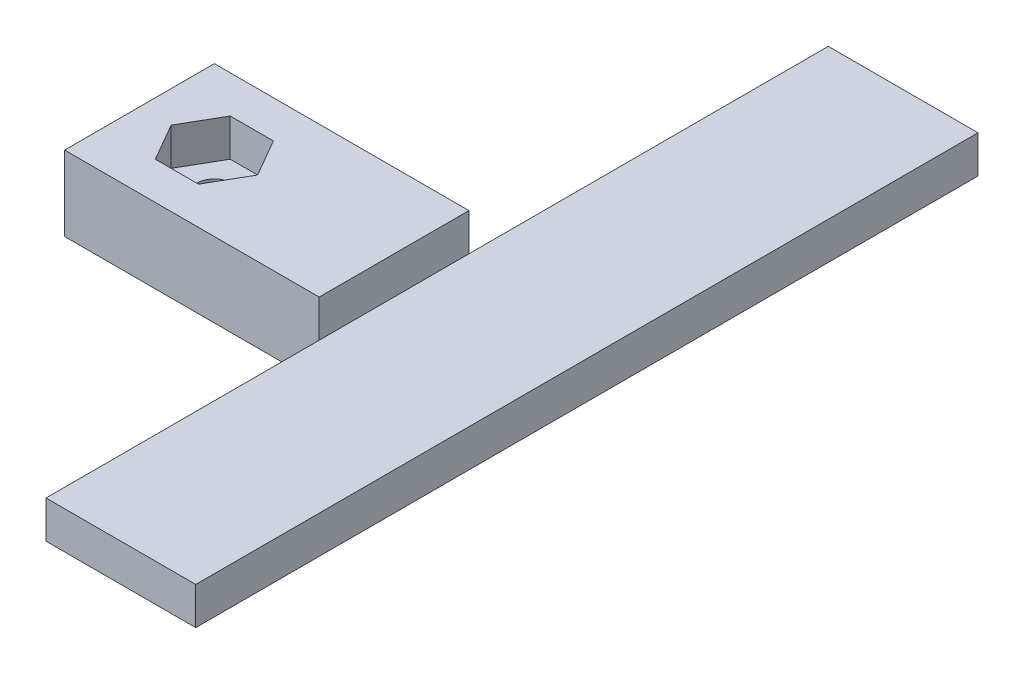
SolidWorks part; units mm, degrees
ref_plane "Front Plane" through (0, 0, 0) normal (0, 0, 1) x (1, 0, 0)
ref_plane "Top Plane" through (0, 0, 0) normal (0, 1, 0) x (1, 0, 0)
ref_plane "Right Plane" through (0, 0, 0) normal (1, 0, 0) x (0, 0, -1)
sketch "Sketch1" plane through (0, 0, 0) normal (0, 1, 0) x (1, 0, 0)
  line L0 (-10.795, 6.35) -> (-10.795, -6.35) construction
  line L1 (17.145, -6.35) -> (-17.145, -6.35)
  line L2 (17.145, -6.35) -> (17.145, 6.35)
  line L3 (17.145, 6.35) -> (-17.145, 6.35)
  line L4 (-17.145, -6.35) -> (-17.145, 6.35)
  line L5 (17.145, -6.35) -> (-17.145, 6.35) construction
  line L6 (17.145, 6.35) -> (-17.145, -6.35) construction
  line L11 (17.145, 36.83) -> (4.445, 36.83)
  line L12 (17.145, 36.83) -> (17.145, -29.52)
  line L13 (17.145, -29.52) -> (4.445, -29.52)
  line L14 (4.445, 36.83) -> (4.445, -29.52)
  line L16 (-8.9619, -3.175) -> (-7.1288, 0)
  line L17 (-7.1288, 0) -> (-8.9619, 3.175)
  line L18 (-8.9619, 3.175) -> (-12.6281, 3.175)
  line L19 (-12.6281, 3.175) -> (-14.4612, 0)
  line L20 (-14.4612, 0) -> (-12.6281, -3.175)
  line L21 (-12.6281, -3.175) -> (-8.9619, -3.175)
  circle A0 centre (-10.795, 0) radius 1.5
  circle A1 centre (-10.795, 0) radius 3.175 construction
  point P0 (0, 0)
  dimension "D8" = 3
  dimension "D1" = 21.59
  dimension "D2" = 6.35
  dimension "D3" = 12.7
  dimension "D4" = 66.35
  dimension "D5" = 30.48
  dimension "D6" = 35.87
  dimension "D7" = 15.24
  dimension "D9" = 6.35
extrude "Boss-Extrude3" add sketch "Sketch1" along normal blind 3.175 contours L14 L3 L4 L1 L21 L20 L19 L18 L17 L16 region at (-5.7013, 0, 0)
extrude "Boss-Extrude4" add sketch "Sketch1<5>" against normal blind 3.175 contours A0 | L3 L4 L1 L2 | L14 L13 L12 L11 region at (-10.795, 0, 0)
sketch "Sketch1<5>" plane through (0, 0, 0) normal (0, 1, 0) x (1, 0, 0) same geometry as "Sketch1"
